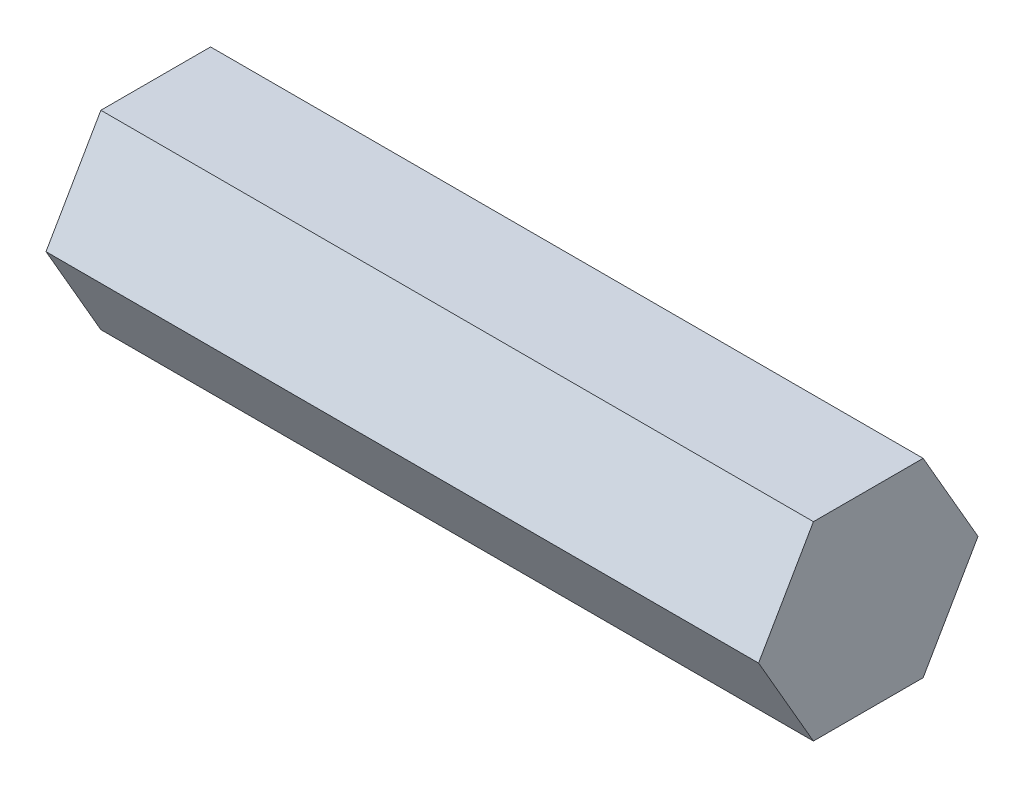
SolidWorks part; units mm, degrees
material "Copper"
ref_plane "Front Plane" through (0, 0, 0) normal (0, 0, 1) x (1, 0, 0)
ref_plane "Top Plane" through (0, 0, 0) normal (0, 1, 0) x (1, 0, 0)
ref_plane "Right Plane" through (0, 0, 0) normal (1, 0, 0) x (0, 0, -1)
sketch "Sketch1" plane through (0, 0, 0) normal (1, 0, 0) x (0, 0, -1)
  circle A0 centre (0, 0) radius 2
  dimension "D1" = 4
extrude "Boss-Extrude1" add sketch "Sketch1" along normal blind 15
ref_axis "Axis1" through (-1.1866, 0, 0) along (-1, 0, 0)
sketch "Sketch2" plane through (15, 0, 0) normal (1, 0, 0) x (0, 0, -1)
  line L1 (2.3094, 0) -> (1.1547, 2)
  line L2 (1.1547, 2) -> (-1.1547, 2)
  line L3 (-1.1547, 2) -> (-2.3094, 0)
  line L4 (-2.3094, 0) -> (-1.1547, -2)
  line L5 (-1.1547, -2) -> (1.1547, -2)
  line L6 (1.1547, -2) -> (2.3094, 0)
  circle A0 centre (0, 0) radius 2 construction
  dimension "D1" = 4
extrude "Boss-Extrude2" add sketch "Sketch2" against normal through all
